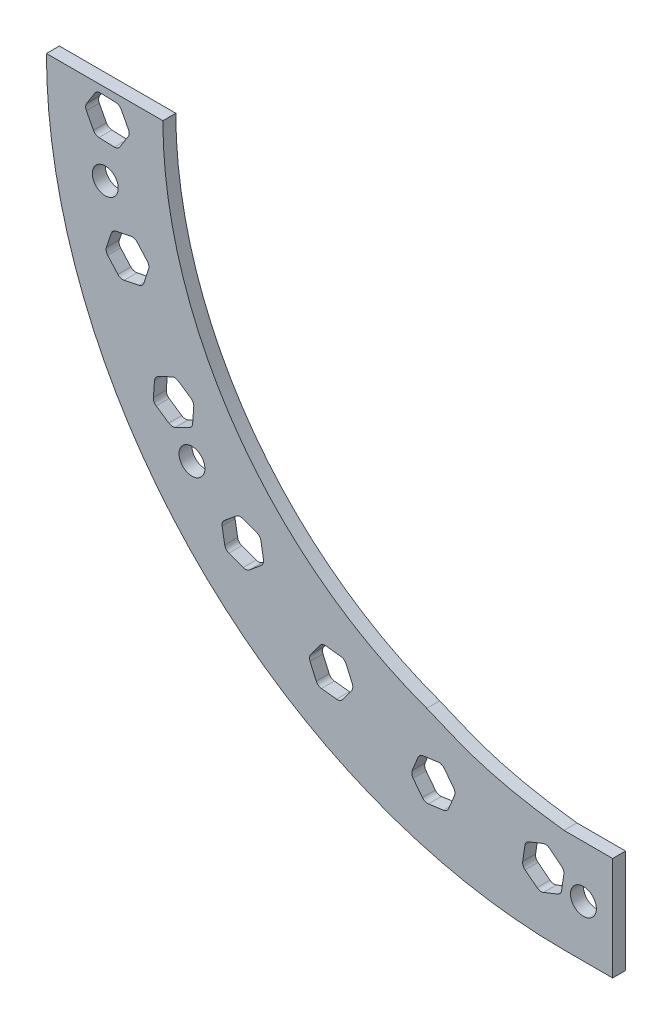
SolidWorks part; units mm, degrees
ref_plane "Front Plane" through (0, 0, 0) normal (0, 0, 1) x (1, 0, 0)
ref_plane "Top Plane" through (0, 0, 0) normal (0, 1, 0) x (1, 0, 0)
ref_plane "Right Plane" through (0, 0, 0) normal (1, 0, 0) x (0, 0, -1)
sketch "Layout" plane through (0, 0, 0) normal (0, 0, 1) x (1, 0, 0)
  line L0 (0, 0) -> (-76.2, 0) construction
  line L1 (-76.2, 0) -> (-203.2, 0) construction
  dimension "D1" = 76.2
  dimension "D2" = 127
sketch "Sketch1" plane through (0, 0, 0) normal (0, 0, 1) x (1, 0, 0)
  line L0 (0, 0) -> (-203.2, 0) construction
  line L1 (0, 0) -> (0, -203.2) construction
  line L2 (0, -203.2) -> (76.2, -203.2)
  line L3 (0, -254) -> (76.2, -254)
  line L4 (-254, 0) -> (-203.2, 0)
  line L5 (76.2, -203.2) -> (76.2, -254)
  arc A0 (-203.2, 0) -> (0, -203.2) centre (0, 0) ccw
  arc A1 (-254, 0) -> (0, -254) centre (0, 0) ccw
  dimension "D1" = 50.8
  dimension "D2" = 76.2
  dimension "D3" = 203.2
extrude "Boss-Extrude1" add sketch "Sketch1" along normal blind 6.35
sketch "Mid_Point_Sk" plane through (0, 0, 0) normal (0, 1, 0) x (1, 0, 0)
  line L0 (-254, 0) -> (-203.2, -6.35) construction
  line L1 (-254, -6.35) -> (-203.2, 0) construction
ref_point "Mid_Point"
ref_plane "Mid_Plane" through (0, 0, 3.175) normal (0, 0, 1) x (1, 0, 0)
sketch "Sketch2" plane through (0, 0, 6.35) normal (0, 0, 1) x (1, 0, 0)
  line L0 (0, 0) -> (-229.3095, 0) construction
  line L1 (0, 0) -> (-222.5647, -39.2442) construction
  line L2 (0, 0) -> (-173.1246, -145.2688) construction
  arc A0 (-222.5647, -39.2442) -> (-173.1246, -145.2688) centre (0, 0) ccw construction
  arc A1 (-222.5647, -39.2442) -> (-173.1246, -145.2688) centre (0, 0) ccw construction
  arc A2 (-228.8182, -40.3468) -> (-177.989, -149.3505) centre (0, 0) ccw
  arc A3 (-216.3112, -38.1415) -> (-168.2602, -141.1871) centre (0, 0) ccw
  arc A4 (-216.3112, -38.1415) -> (-228.8182, -40.3468) centre (-222.5647, -39.2442) ccw
  arc A5 (-177.989, -149.3505) -> (-168.2602, -141.1871) centre (-173.1246, -145.2688) ccw
  point P5 (-204.8238, -95.5109)
  dimension "D1" = 30
  dimension "D3" = 12.7
  dimension "D2" = 10
sketch "Sketch3" plane through (0, 0, 6.35) normal (0, 0, 1) x (1, 0, 0)
  line L0 (0, 0) -> (-225.1271, -39.696) construction
  line L1 (0, 0) -> (-182.5681, -137.5749) construction
  line L2 (-203.2, 0) -> (-254, 0) construction
  circle A1 centre (-182.5681, -137.5749) radius 6.35
  circle A3 centre (-225.1271, -39.696) radius 6.35
  dimension "D1" = 228.6
  dimension "D2" = 27
  dimension "D3" = 10
extrude "Cut-Extrude1" cut sketch "Sketch3" against normal up to next
sketch "Sketch4" plane through (0, 0, 6.35) normal (0, 0, 1) x (1, 0, 0)
  line L0 (0, -203.2) -> (0, -228.6) construction
  line L1 (0, -228.6) -> (9.525, -228.6) construction
  circle A1 centre (9.525, -228.6) radius 6.35
  dimension "D1" = 25.4
  dimension "D2" = 9.525
extrude "Cut-Extrude2" cut sketch "Sketch4" against normal up to next
sketch "Sketch5" plane through (0, 0, 6.35) normal (0, 0, 1) x (1, 0, 0)
  line L0 (0, 0) -> (-67.3267, -184.9785) construction
  line L2 (0, 0) -> (-196.85, 0) construction
  line L3 (-196.85, 0) -> (-203.2, 0)
  arc A0 (-67.3267, -184.9785) -> (-196.85, 0) centre (0, 0) cw
  arc A1 (-203.2, 0) -> (0, -203.2) centre (0, 0) ccw construction
  arc A2 (-203.2, 0) -> (0, -203.2) centre (0, 0) ccw
  spline S0 degree 3 poles (0, -203.2) (-42.7386, -198.0277) (-55.3777, -189.3302) (-67.3267, -184.9785) knots 0 0 0 0 1 1 1 1
  dimension "D1" = 70
  dimension "D2" = 196.85
extrude "Boss-Extrude2" add sketch "Sketch5" against normal up to surface (6.35 mm away) up to face at (15.875, -228.6, 0)
sketch "Sketch6" plane through (0, 0, 6.35) normal (0, 0, 1) x (1, 0, 0)
  line L0 (-204.5101, -63.4989) -> (-209.4922, -57.9153)
  line L1 (-217.9162, -21.638) -> (-213.9222, -15.3098)
  line L3 (-213.797, -12.1373) -> (-217.2803, -5.5142)
  line L4 (-219.9653, -3.8196) -> (-227.4427, -3.5247)
  line L5 (-230.2527, -5.0026) -> (-234.2468, -11.3308)
  line L6 (-234.3719, -14.5033) -> (-230.8886, -21.1264)
  line L7 (-228.2037, -22.821) -> (-220.7263, -23.1159)
  line L8 (-206.2085, -73.714) -> (-203.864, -66.6075)
  line L9 (-215.9042, -77.3506) -> (-208.5776, -75.8278)
  line L10 (-223.9014, -70.7722) -> (-218.9193, -76.3558)
  line L11 (-222.203, -60.5572) -> (-224.5475, -67.6636)
  line L12 (-212.5073, -56.9206) -> (-219.8339, -58.4434)
  line L13 (-183.0735, -111.0882) -> (-189.2584, -106.8757)
  line L14 (-182.2502, -121.4107) -> (-181.6945, -113.9481)
  line L15 (-190.7781, -127.2849) -> (-184.0375, -124.0348)
  line L16 (-200.1293, -122.8366) -> (-193.9443, -127.0491)
  line L17 (-200.9525, -112.5141) -> (-201.5082, -119.9767)
  line L18 (-192.4246, -106.6399) -> (-199.1652, -109.89)
  line L19 (-150.7607, -152.0779) -> (-157.781, -149.4868)
  line L20 (-147.4647, -161.8946) -> (-148.7309, -154.5193)
  line L21 (-154.3182, -169.6574) -> (-148.5641, -164.8732)
  line L22 (-164.4677, -167.6035) -> (-157.4474, -170.1946)
  line L23 (-167.7637, -157.7868) -> (-166.4975, -165.1621)
  line L24 (-160.9102, -150.024) -> (-166.6644, -154.8082)
  line L25 (-109.4915, -184.0329) -> (-116.9301, -183.2171)
  line L26 (-103.9185, -192.7606) -> (-106.9313, -185.9107)
  line L27 (-108.6904, -201.9508) -> (-104.2646, -195.9166)
  line L28 (-119.0353, -202.4133) -> (-111.5967, -203.2291)
  line L29 (-124.6083, -193.6856) -> (-121.5955, -200.5355)
  line L30 (-119.8364, -184.4954) -> (-124.2622, -190.5295)
  line L31 (-61.7176, -205.0547) -> (-69.1326, -206.0627)
  line L32 (-54.1987, -212.1749) -> (-58.7792, -206.2573)
  line L33 (-56.6055, -222.2466) -> (-53.771, -215.321)
  line L34 (-66.5313, -225.198) -> (-59.1163, -224.19)
  line L35 (-74.0502, -218.0778) -> (-69.4697, -223.9954)
  line L36 (-71.6433, -208.0061) -> (-74.4778, -214.9317)
  line L37 (-10.2771, -213.8945) -> (-17.228, -216.6664)
  line L38 (-1.259, -218.9843) -> (-7.135, -214.3506)
  line L39 (-1.1578, -229.339) -> (-0.0829, -221.9334)
  line L40 (-10.0747, -234.604) -> (-3.1238, -231.8321)
  line L41 (-19.0928, -229.5143) -> (-13.2168, -234.148)
  line L42 (-19.194, -219.1595) -> (-20.2688, -226.5651)
  line L43 (0, 0) -> (-213.797, -12.1373) construction
  line L44 (0, 0) -> (-204.5101, -63.4989) construction
  circle A0 centre (-224.0845, -13.3203) radius 9.6556 construction
  arc A1 (-209.4922, -57.9153) -> (-212.5073, -56.9206) centre (-211.8612, -60.0291) ccw
  arc A2 (-203.864, -66.6075) -> (-204.5101, -63.4989) centre (-206.8791, -65.6128) ccw
  arc A3 (-206.2085, -73.714) -> (-208.5776, -75.8278) centre (-209.2236, -72.7192) cw
  arc A4 (-218.9193, -76.3558) -> (-215.9042, -77.3506) centre (-216.5503, -74.242) ccw
  arc A5 (-224.5475, -67.6636) -> (-223.9014, -70.7722) centre (-221.5324, -68.6584) ccw
  arc A6 (-219.8339, -58.4434) -> (-222.203, -60.5572) centre (-219.1878, -61.5519) ccw
  arc A7 (-217.9162, -21.638) -> (-220.7263, -23.1159) centre (-220.6012, -19.9434) cw
  arc A8 (-230.8886, -21.1264) -> (-228.2037, -22.821) centre (-228.0786, -19.6485) ccw
  arc A9 (-234.2468, -11.3308) -> (-234.3719, -14.5033) centre (-231.5619, -13.0254) ccw
  arc A10 (-227.4427, -3.5247) -> (-230.2527, -5.0026) centre (-227.5678, -6.6972) ccw
  arc A11 (-217.2803, -5.5142) -> (-219.9653, -3.8196) centre (-220.0904, -6.9921) ccw
  arc A12 (-213.9222, -15.3098) -> (-213.797, -12.1373) centre (-216.6071, -13.6152) ccw
  arc A13 (-189.2584, -106.8757) -> (-192.4246, -106.6399) centre (-191.0457, -109.4999) ccw
  arc A14 (-181.6945, -113.9481) -> (-183.0735, -111.0882) centre (-184.8608, -113.7124) ccw
  arc A15 (-182.2502, -121.4107) -> (-184.0375, -124.0348) centre (-185.4164, -121.1749) cw
  arc A16 (-193.9443, -127.0491) -> (-190.7781, -127.2849) centre (-192.157, -124.425) ccw
  arc A17 (-201.5082, -119.9767) -> (-200.1293, -122.8366) centre (-198.342, -120.2125) ccw
  arc A18 (-199.1652, -109.89) -> (-200.9525, -112.5141) centre (-197.7863, -112.7499) ccw
  arc A19 (-157.781, -149.4868) -> (-160.9102, -150.024) centre (-158.8804, -152.4654) ccw
  arc A20 (-148.7309, -154.5193) -> (-150.7607, -152.0779) centre (-151.8601, -155.0565) ccw
  arc A21 (-147.4647, -161.8946) -> (-148.5641, -164.8732) centre (-150.5939, -162.4318) cw
  arc A22 (-157.4474, -170.1946) -> (-154.3182, -169.6574) centre (-156.348, -167.216) ccw
  arc A23 (-166.4975, -165.1621) -> (-164.4677, -167.6035) centre (-163.3683, -164.6249) ccw
  arc A24 (-166.6644, -154.8082) -> (-167.7637, -157.7868) centre (-164.6345, -157.2496) ccw
  arc A25 (-116.9301, -183.2171) -> (-119.8364, -184.4954) centre (-117.2762, -186.3732) ccw
  arc A26 (-106.9313, -185.9107) -> (-109.4915, -184.0329) centre (-109.8376, -187.1889) ccw
  arc A27 (-103.9185, -192.7606) -> (-104.2646, -195.9166) centre (-106.8248, -194.0389) cw
  arc A28 (-111.5967, -203.2291) -> (-108.6904, -201.9508) centre (-111.2506, -200.073) ccw
  arc A29 (-121.5955, -200.5355) -> (-119.0353, -202.4133) centre (-118.6892, -199.2572) ccw
  arc A30 (-124.2622, -190.5295) -> (-124.6083, -193.6856) centre (-121.702, -192.4073) ccw
  arc A31 (-69.1326, -206.0627) -> (-71.6433, -208.0061) centre (-68.7049, -209.2088) ccw
  arc A32 (-58.7792, -206.2573) -> (-61.7176, -205.0547) centre (-61.2899, -208.2008) ccw
  arc A33 (-54.1987, -212.1749) -> (-53.771, -215.321) centre (-56.7094, -214.1183) cw
  arc A34 (-59.1163, -224.19) -> (-56.6055, -222.2466) centre (-59.544, -221.0439) ccw
  arc A35 (-69.4697, -223.9954) -> (-66.5313, -225.198) centre (-66.959, -222.0519) ccw
  arc A36 (-74.4778, -214.9317) -> (-74.0502, -218.0778) centre (-71.5394, -216.1344) ccw
  arc A37 (-17.228, -216.6664) -> (-19.194, -219.1595) centre (-16.0519, -219.6156) ccw
  arc A38 (-7.135, -214.3506) -> (-10.2771, -213.8945) centre (-9.101, -216.8437) ccw
  arc A39 (-1.259, -218.9843) -> (-0.0829, -221.9334) centre (-3.225, -221.4774) cw
  arc A40 (-3.1238, -231.8321) -> (-1.1578, -229.339) centre (-4.2999, -228.883) ccw
  arc A41 (-13.2168, -234.148) -> (-10.0747, -234.604) centre (-11.2508, -231.6549) ccw
  arc A42 (-20.2688, -226.5651) -> (-19.0928, -229.5143) centre (-17.1268, -227.0212) ccw
  point P12 (0, 0)
  point P75 (-212.9438, -13.7597)
  dimension "D1" = 14
  dimension "D2" = 3.175
extrude "Cut-Extrude3" cut sketch "Sketch6" against normal through all
sketch "Sketch7" plane through (0, 0, 6.35) normal (0, 0, 1) x (1, 0, 0)
  line L0 (76.2, -203.2) -> (0, -203.2) construction
  line L1 (76.2, -254) -> (23.876, -254)
  line L2 (76.2, -254) -> (76.2, -203.2)
  line L3 (76.2, -203.2) -> (23.876, -203.2)
  line L4 (23.876, -254) -> (23.876, -203.2)
  dimension "D1" = 52.324
extrude "Cut-Extrude4" cut sketch "Sketch7" against normal through all
